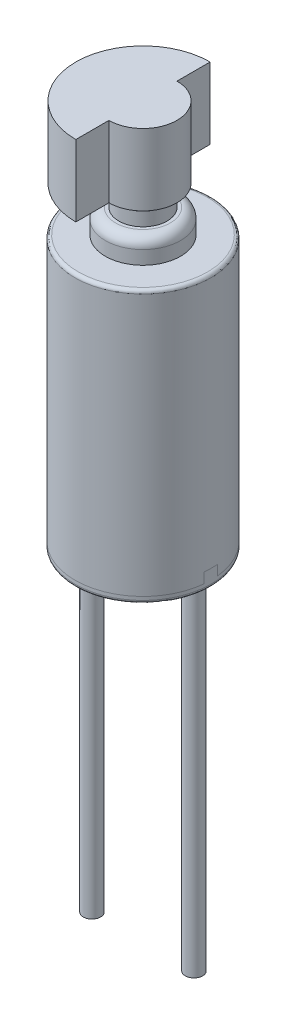
SolidWorks part; units mm, degrees
ref_plane "Front Plane" through (0, 0, 0) normal (0, 0, 1) x (1, 0, 0)
ref_plane "Top Plane" through (0, 0, 0) normal (0, 1, 0) x (1, 0, 0)
ref_plane "Right Plane" through (0, 0, 0) normal (1, 0, 0) x (0, 0, -1)
sketch "Sketch1" plane through (0, 0, 0) normal (0, 1, 0) x (1, 0, 0)
  circle A0 centre (0, 0) radius 2
  dimension "D1" = 4
extrude "Boss-Extrude1" add sketch "Sketch1" along normal blind 8
sketch "Sketch2" plane through (0, 8, 0) normal (0, 1, 0) x (1, 0, 0)
  circle A0 centre (0, 0) radius 1.105
  dimension "D1" = 2.21
extrude "Boss-Extrude2" add sketch "Sketch2" along normal blind 0.7
sketch "Sketch3" plane through (0, 8.7, 0) normal (0, 1, 0) x (1, 0, 0)
  circle A0 centre (0, 0) radius 0.71
  dimension "D1" = 1.42
extrude "Boss-Extrude3" add sketch "Sketch3" along normal blind 0.6 separate body
sketch "Sketch4" plane through (0, 9.3, 0) normal (0, 1, 0) x (1, 0, 0)
  circle A0 centre (0, 0) radius 0.335
  dimension "D1" = 0.67
extrude "Boss-Extrude4" add sketch "Sketch4" along normal blind 2.11 separate body
sketch "Sketch5" plane through (0, 0, 0) normal (1, 0, 0) x (0, 0, -1)
  line L0 (-2, 0.2) -> (-0.2, 0.2)
  line L1 (-2, 8) -> (-2, 0) construction
  line L2 (-0.2, 0.2) -> (-0.2, 0.5)
  line L3 (-0.2, 0.5) -> (0.2, 0.5)
  line L4 (0, 2.2) -> (0, -2.2) construction
  line L5 (0.2, 0.2) -> (0.2, 0.5)
  line L6 (2, 0.2) -> (0.2, 0.2)
  line L7 (2.2, 0) -> (-2.2, 0) construction
  point P10 (0, 0.5)
  dimension "D1" = 0.2
  dimension "D2" = 0.4
  dimension "D3" = 0.3
split "Split1" trim tools "Sketch5" bodies to split 102 resulting bodies 105 106
fillet "Fillet1" radius 0.1 1 edges at (0, 0, 2)
fillet "Fillet2" radius 0.1 1 edges at (0, 8, 2)
fillet "Fillet3" radius 0.3 1 edges at (0, 8.7, 1.105)
chamfer "Chamfer1" distance 0.2 angle 45 1 edges at (0, 9.3, 0.71)
fillet "Fillet4" radius 0.1 1 edges at (0, 11.41, 0.335)
sketch "Sketch6" plane through (0, 0, 0) normal (0, -1, 0) x (1, 0, 0)
  line L0 (0, -2.2) -> (0, 2.2) construction
  circle A0 centre (-1.5, 0) radius 0.255
  circle A1 centre (1.5, 0) radius 0.255
  dimension "D1" = 0.51
  dimension "D2" = 1.5
extrude "Boss-Extrude5" add sketch "Sketch6" along normal blind 10 separate body
ref_axis "Axis1" through (0, 7.9, 0) along (0, -1, 0)
sketch "Sketch7" plane through (0, 11.41, 0) normal (0, 1, 0) x (1, 0, 0)
  circle A0 centre (0, 0) radius 1.975
  dimension "D1" = 3.95
extrude "Boss-Extrude6" add sketch "Sketch7" against normal blind 2.1
sketch "Sketch8" plane through (0, 11.41, 0) normal (0, 1, 0) x (1, 0, 0)
  line L0 (0, 2) -> (0, -2)
  circle A0 centre (0, 0) radius 2 construction
  circle A1 centre (0, 0) radius 1
  circle A2 centre (0, 0) radius 1.975
  circle A3 centre (0, 0) radius 1.975 construction
  circle M3 centre (0, 0) radius 1.975
  dimension "D1" = 2
extrude "Cut-Extrude1" cut sketch "Sketch8" against normal up to surface (2.1 mm away) contours A1 L0 M3 region at (1.3653, 11.41, -1.3653) up to face at (0, 9.31, 0.335)
